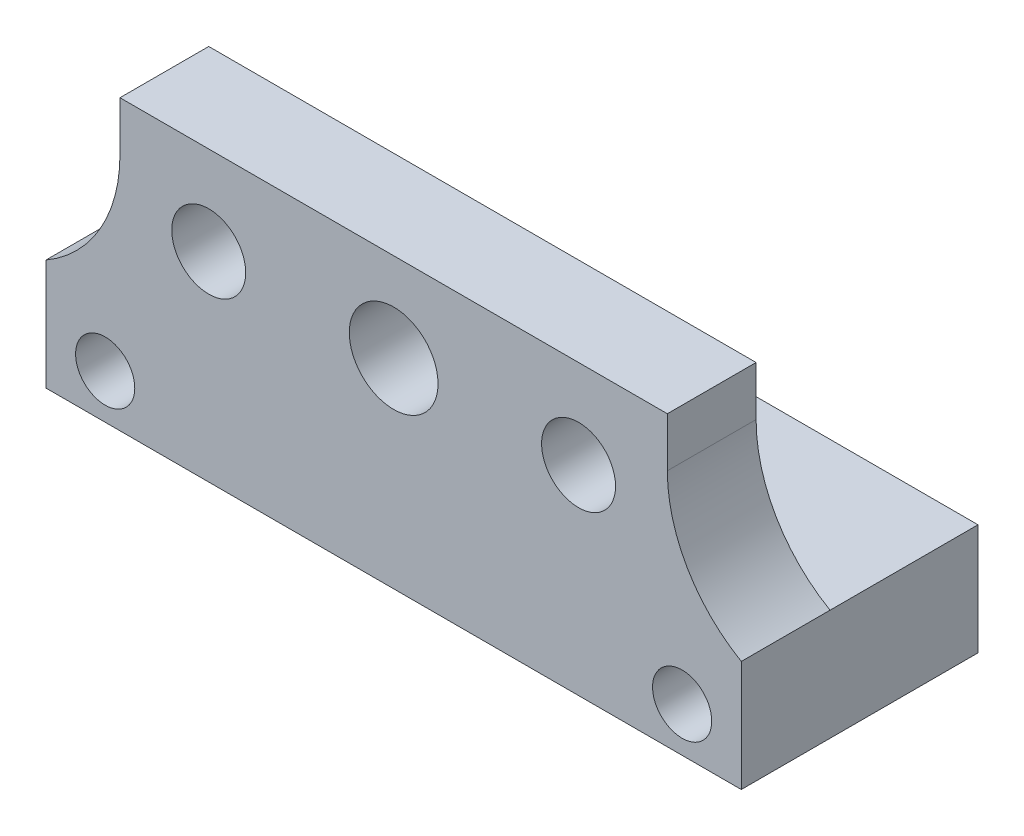
SolidWorks part; units mm, degrees
material "Polyetheretherketone (PEEK)"
ref_plane "Front Plane" through (0, 0, 0) normal (0, 0, 1) x (1, 0, 0)
ref_plane "Top Plane" through (0, 0, 0) normal (0, 1, 0) x (1, 0, 0)
ref_plane "Right Plane" through (0, 0, 0) normal (1, 0, 0) x (0, 0, -1)
ref_plane "Plane1" through (0, 0, 1.2) normal (0, 0, 1) x (1, 0, 0)
sketch "Sketch1" plane through (0, 0, 1.2) normal (0, 0, 1) x (1, 0, 0)
  line L0 (7.4, 2.4) -> (0, 2.4)
  line L1 (0, 2.4) -> (0, 0)
  line L2 (0, 0) -> (7.4, 0)
  line L3 (7.4, 0) -> (7.4, 2.4)
  line L5 (-1, 0) -> (8.4, 0)
  line L6 (-1, 0) -> (-1, -1.5)
  line L7 (-1, -1.5) -> (8.4, -1.5)
  line L8 (8.4, 0) -> (8.4, -1.5)
  point P8 (3.7, 0)
  point P9 (3.7, 0)
  dimension "D1" = 1.5
  dimension "D2" = 9.4
  dimension "D3" = 7.4
  dimension "D4" = 2.4
extrude "Boss-Extrude1" add sketch "Sketch1" against normal blind 1.2 contours L2 L3 L0 L1 | L8 L5 L2 L6 L7 region at (3.7, 1.2, 1.2) region at (3.7, -0.75, 1.2)
hole_wizard "Hole1" positions "Sketch8" profile "Sketch7" legacy end condition through all
sketch "Sketch8" plane through (0, 0, 1.2) normal (0, 0, 1) x (1, 0, 0)
  point P0 (6.2, 1.2)
  point P2 (1.2, 1.2)
  dimension "D1" = 1.2
  dimension "D2" = 1.2
  dimension "D3" = 5
sketch "Sketch7" plane through (6.2, 1.2, 1.2) normal (1, 0, 0) x (0, -1, 0)
  line L0 (0, 0) -> (0, 1.3803)
  line L1 (0, 1.3803) -> (0.3, 1.2)
  line L2 (0.3, 1.2) -> (0.3, 0.9)
  line L3 (0.3, 0.9) -> (0.5, 0.9)
  line L4 (0.5, 0) -> (0, 0)
  line L5 (0, -11.3109) -> (0, 121.1557) construction
  line L6 (0, 1.3803) -> (-0.3, 1.2) construction
  line L7 (0.5, 0.9) -> (0.5, 0)
  dimension "Depth" = 1.2
  dimension "Drill Angle" = 118
  dimension "Diameter" = 0.6
  dimension "C-Bore Diameter" = 1
  dimension "C-Bore Depth" = 0.9
sketch "Sketch11" plane through (0, 0, 0) normal (0, 0, -1) x (-1, 0, 0)
  line L1 (-8.4, 0) -> (1, 0)
  line L2 (-8.4, 0) -> (-8.4, -1.5)
  line L3 (-8.4, -1.5) -> (1, -1.5)
  line L4 (1, 0) -> (1, -1.5)
  dimension "D1" = 9.4
extrude "Boss-Extrude5" add sketch "Sketch11" along normal blind 2
fillet "Fillet1" radius 2 2 edges
hole_wizard "Ø0.8 (0.8) Diameter Hole1" positions "Sketch17" profile "Sketch16" hole size "Ø0.8" standard "ISO" end condition through all
sketch "Sketch17" plane through (0, 0, 1.2) normal (0, 0, 1) x (1, 0, 0)
  line L0 (-1, 0) -> (-1, -1.5) construction
  line L2 (8.4, -1.5) -> (-1, -1.5) construction
  point P0 (-0.2, -0.9)
  point P2 (7.6, -0.9)
  dimension "D1" = 7.8
  dimension "D2" = 0.8
  dimension "D3" = 0.6
sketch "Sketch16" plane through (-0.2, -0.9, 1.2) normal (1, 0, 0) x (0, -1, 0)
  line L0 (0, 0) -> (0, 3.2)
  line L1 (0, 3.2) -> (0.4, 3.2)
  line L2 (0.4, 3.2) -> (0.4, 0)
  line L5 (0.4, 0) -> (0, 0)
  line L11 (0, -6.35) -> (0, 107.95) construction
  dimension "Thru Hole Dia." = 0.8
  dimension "Thru Hole Depth" = 3.2
hole_wizard "M1.0 Clearance Hole1" positions "Sketch18" profile "Sketch19" hole size "M1.0" standard "ANSI Metric" end condition up to next
sketch "Sketch18" plane through (0, 0, 1.2) normal (0, 0, 1) x (1, 0, 0)
  line L0 (6.2, 1.2) -> (1.2, 1.2) construction
  circle A0 centre (6.2, 1.2) radius 0.3 construction
  circle A1 centre (6.2, 1.2) radius 0.3
  circle A2 centre (1.2, 1.2) radius 0.3 construction
  circle A3 centre (1.2, 1.2) radius 0.3
  point P13 (3.7, 1.2)
  point P16 (0, 0)
sketch "Sketch19" plane through (3.7, 1.2, 1.2) normal (1, 0, 0) x (0, -1, 0)
  line L0 (0, 0) -> (0, 1.2)
  line L1 (0, 1.2) -> (0.6, 1.2)
  line L2 (0.6, 1.2) -> (0.6, 0)
  line L5 (0.6, 0) -> (0, 0)
  line L11 (0, -6.35) -> (0, 107.95) construction
  dimension "Thru Hole Dia." = 1.2
  dimension "Thru Hole Depth" = 1.2
